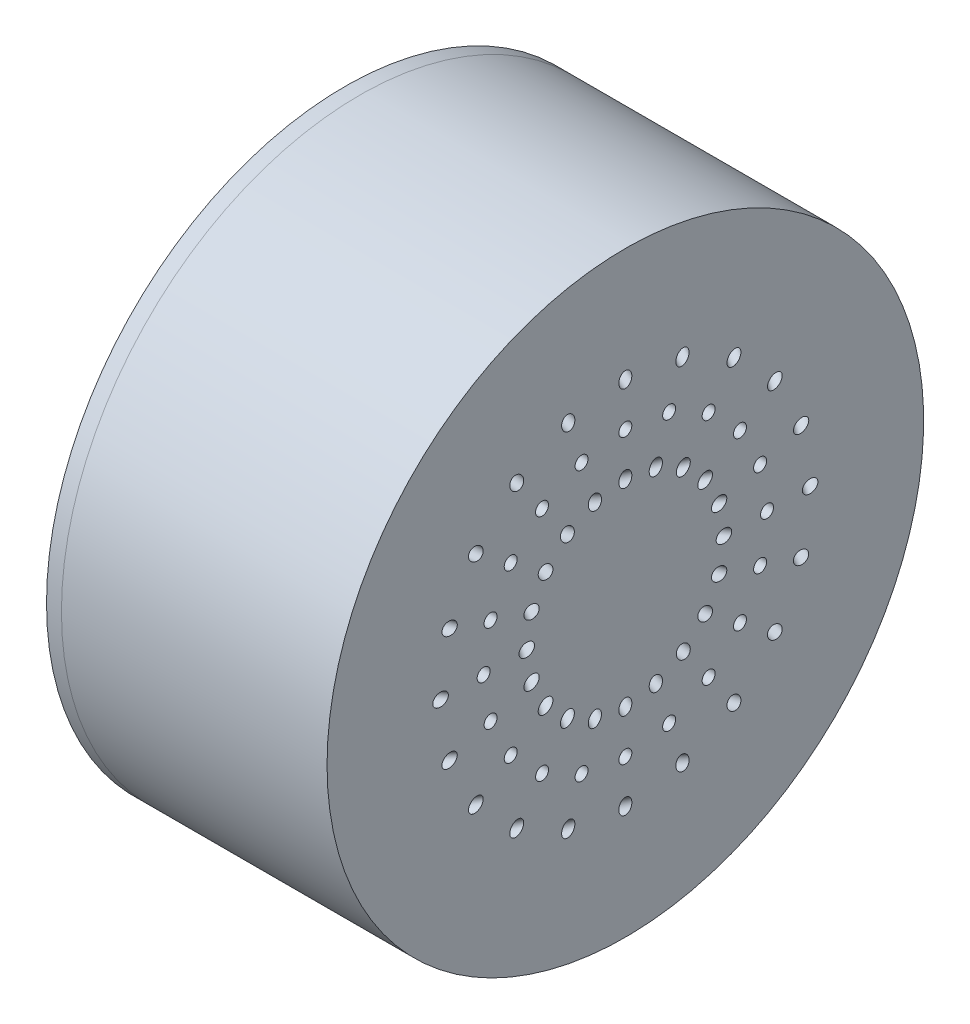
SolidWorks part; units mm, degrees
note: The reader was unsure of these and kept them because the rebuilt part matched: shared geometry of "Sketch3<13>".
material "6061-T6 (SS)"
ref_plane "Front Plane" through (0, 0, 0) normal (0, 0, 1) x (1, 0, 0)
ref_plane "Top Plane" through (0, 0, 0) normal (0, 1, 0) x (1, 0, 0)
ref_plane "Right Plane" through (0, 0, 0) normal (1, 0, 0) x (0, 0, -1)
sketch "Sketch3" plane through (0, 0, 0) normal (0, 0, 1) x (1, 0, 0)
  line L0 (0, 50.8) -> (0, 0)
  line L1 (0, 50.8) -> (-45.2298, 50.8)
  line L2 (0, 31.4667) -> (-17.6708, 43.2058) construction
  line L3 (-52.0956, 0) -> (66.415, 0) construction
  line L4 (-17.6708, 41.88) -> (0, 30.1409)
  line L5 (0, 24.13) -> (11.0439, 24.13) construction
  line L6 (-45.2298, 36.4109) -> (11.0439, 36.4109) construction
  line L7 (0, 31.4667) -> (11.0439, 24.13) construction
  line L8 (-17.6708, 29.6418) -> (-45.2298, 29.6418)
  line L9 (-17.6708, 18.6182) -> (-45.2298, 18.6182)
  line L10 (-22.7508, 18.6182) -> (-22.7508, 24.13) construction
  line L11 (-45.2298, 48.26) -> (-17.6708, 48.26)
  line L12 (-17.6708, 48.26) -> (-17.6708, 32.1818)
  line L13 (-17.6708, 23.0251) -> (0, 23.0251)
  line L14 (0, 30.1409) -> (0, 32.7926)
  line L15 (0, 16.7933) -> (11.0439, 24.13) construction
  line L16 (-22.7508, 24.13) -> (-22.7508, 29.6418) construction
  line L17 (-45.2298, 32.1818) -> (-17.6708, 32.1818)
  line L18 (-45.2298, 0) -> (-45.2298, 50.8)
  line L19 (-45.2298, 16.0782) -> (-17.6708, 16.0782)
  line L20 (-22.7508, 32.1818) -> (-22.7508, 48.26) construction
  line L21 (-22.7508, 16.0782) -> (-22.7508, 0) construction
  line L22 (-17.6708, 29.6418) -> (-17.6708, 18.6182)
  line L23 (-17.6708, 16.0782) -> (-17.6708, 0)
  line L24 (-17.6708, 0) -> (0, 0)
  line L25 (-17.6708, 5.0542) -> (0, 16.7933) construction
  line L26 (0, 32.7926) -> (-17.6708, 44.5317)
  line L27 (-17.6708, 44.5317) -> (-17.6708, 41.88)
  line L28 (-8.8354, 36.0104) -> (-8.8354, 38.6622) construction
  line L29 (-17.6708, 6.38) -> (0, 18.1191)
  line L30 (0, 18.1191) -> (0, 15.4674)
  line L31 (0, 15.4674) -> (-17.6708, 3.7283)
  line L32 (-17.6708, 3.7283) -> (-17.6708, 6.38)
  line L33 (-8.8354, 12.2496) -> (-8.8354, 9.5978) construction
  line L34 (-17.6708, 24.13) -> (0, 24.13) construction
  line L35 (0, 23.0251) -> (0, 25.2349)
  line L36 (0, 25.2349) -> (-17.6708, 25.2349)
  line L37 (-17.6708, 25.2349) -> (-17.6708, 23.0251)
  line L38 (-8.8354, 25.2349) -> (-8.8354, 23.0251) construction
  line L39 (-17.6708, 43.2058) -> (0, 31.4667)
  line L40 (0, 24.13) -> (-17.6708, 24.13)
  line L41 (0, 16.7933) -> (-17.6708, 5.0542)
  line L43 (-45.2298, 50.8) -> (-47.7698, 50.8)
  line L44 (-45.2298, 50.8) -> (-45.2298, 0)
  line L45 (-45.2298, 0) -> (-47.7698, 0)
  line L46 (-47.7698, 50.8) -> (-47.7698, 0)
  point P20 (0, 24.13)
  point P21 (0, 16.7933)
  point P22 (0, 31.4667)
  point P43 (-8.8354, 37.3363)
  point P46 (-8.8354, 38.6622)
  point P51 (-8.8354, 10.9237)
  point P52 (-8.8354, 10.9237)
  point P59 (-8.8354, 24.13)
  point P60 (-8.8354, 24.13)
  dimension "D1" = 50.8
  dimension "D2" = 36.4109
  dimension "D3" = 11.0439
  dimension "D4" = 13.2588
  dimension "D5" = 27.559
  dimension "D6" = 2.54
  dimension "D7" = 17.6708
  dimension "D8" = 2.6518
  dimension "D9" = 11.0236
  dimension "D10" = 2.54
  dimension "D11" = 2.54
  dimension "D12" = 5.08
  dimension "D13" = 2.6518
  dimension "D14" = 2.2098
  dimension "D15" = 2.54
revolve "Revolve1" add sketch "Sketch3" angle 360 about L3
revolve "Revolve2" add sketch "Sketch3<13>" angle 360 about L3
sketch "Sketch3<13>" plane through (0, 0, 0) normal (0, 0, 1) x (1, 0, 0) same geometry as "Sketch3"
ref_plane "Plane1" through (0, 31.4667, 0) normal (0.833, -0.5533, 0) x (0, 0, -1)
ref_plane "Plane2" through (0, 16.7933, 0) normal (0.833, 0.5533, 0) x (0, 0, -1)
sketch "Sketch5" plane through (0, 31.4667, 0) normal (0.833, -0.5533, 0) x (0, 0, -1)
  circle A1 centre (0, 0) radius 1.1044
  dimension "D1" = 2.2088
sketch "Sketch6" plane through (0, 16.7933, 0) normal (0.833, 0.5533, 0) x (0, 0, -1)
  line L0 (0, -1.1044) -> (0, 1.1044) construction
  circle A0 centre (0, 0) radius 1.1044
  dimension "D1" = 2.2088
sketch "Sketch7" plane through (0, 0, 0) normal (1, 0, 0) x (0, 0, -1)
  circle A0 centre (0, 24.13) radius 1.1049
  dimension "D1" = 2.2098
extrude "Cut-Extrude2" cut sketch "Sketch5" against normal up to surface and the other way through all
extrude "Cut-Extrude3" cut sketch "Sketch7" against normal through all both and the other way through all
extrude "Cut-Extrude4" cut sketch "Sketch6" against normal up to surface and the other way through all
pattern_circular "CirPattern1" count 20 over 360 about axis through (0, 0, 0) along (1, 0, 0) of "Cut-Extrude4", "Cut-Extrude3", "Cut-Extrude2"
